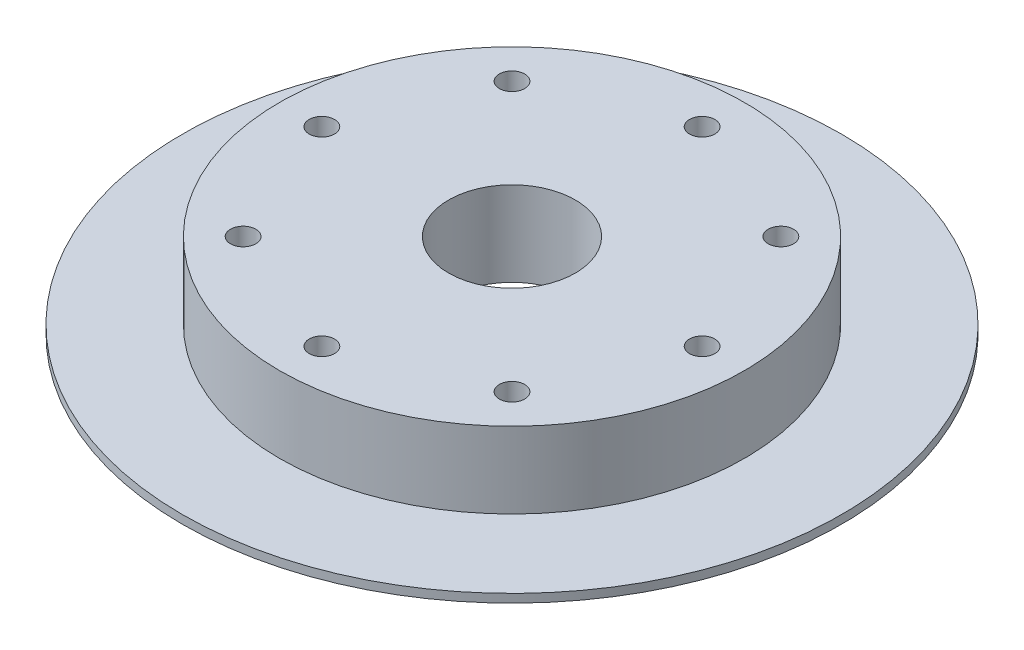
SolidWorks part; units mm, degrees
ref_plane "Front Plane" through (0, 0, 0) normal (0, 0, 1) x (1, 0, 0)
ref_plane "Top Plane" through (0, 0, 0) normal (0, 1, 0) x (1, 0, 0)
ref_plane "Right Plane" through (0, 0, 0) normal (1, 0, 0) x (0, 0, -1)
sketch "Sketch1" plane through (0, 0, 0) normal (0, 1, 0) x (1, 0, 0)
  line L0 (0, 0) -> (22.5, 0) construction
  circle A0 centre (0, 0) radius 39
  circle A1 centre (22.5, 0) radius 1.5
  circle A2 centre (15.9099, -15.9099) radius 1.5
  circle A3 centre (0, -22.5) radius 1.5
  circle A4 centre (-15.9099, -15.9099) radius 1.5
  circle A5 centre (-22.5, 0) radius 1.5
  circle A6 centre (-15.9099, 15.9099) radius 1.5
  circle A7 centre (0, 22.5) radius 1.5
  circle A8 centre (15.9099, 15.9099) radius 1.5
  circle A9 centre (0, 0) radius 7.5
  circle A10 centre (0, 0) radius 27.5
  point P14 (0, 0)
  dimension "D2" = 78
  dimension "D3" = 15
  dimension "D5" = 3
  dimension "D6" = 55
  dimension "D4" = 22.5
  dimension "D1" = 8
extrude "Boss-Extrude1" add sketch "Sketch1" against normal blind 1 contours A0 A10 | A10 A2 A3 A4 A5 A6 A7 A8 A9 A1 region at (-37.8969, 0, 0) region at (-26.7222, 0, 0)
extrude "Boss-Extrude2" add sketch "Sketch1<3>" along normal blind 9 contours A10 A2 A3 A4 A5 A6 A7 A8 A9 A1 region at (-26.7222, 0, 0)
sketch "Sketch1<3>" plane through (0, 0, 0) normal (0, 1, 0) x (1, 0, 0) same geometry as "Sketch1"
equation "\"bearing_21_OD\"= 21mm"
equation "\"pin_cirlce_diameter\"= 75mm"
equation "\"pin_diam\"= 6mm"
equation "\"gear_thickness\"= 4mm"
equation "\"ball_bearing_diam\"= 2.96mm"
equation "\"bearing_21_outer_clearance\"= 0mm'change this"
equation "\"bearing_15_OD\"= 15mm"
equation "\"bearing_15_outer_clearance\"= 0mm'change this"
equation "\"thrust_bearing_thickness\"= 5mm'measure this irl and change"
equation "\"D3@Sketch1\"=\"bearing_15_OD\" +\"bearing_15_outer_clearance\""
equation "\"D1@Boss-Extrude2\"=\"thrust_bearing_thickness\"+4mm"
